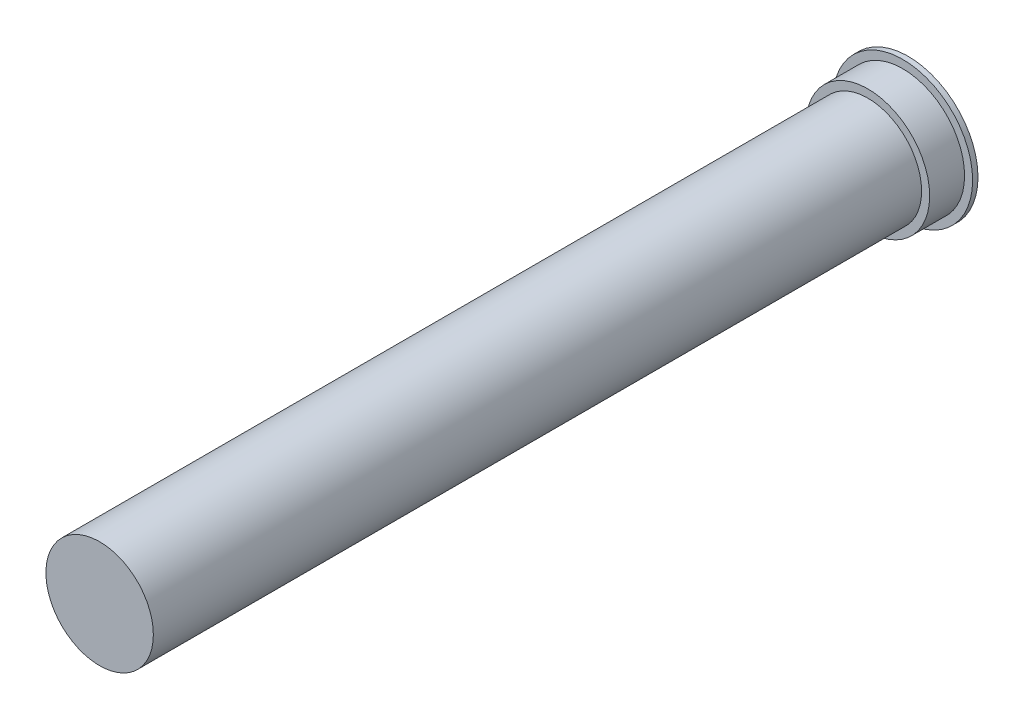
SolidWorks part; units mm, degrees
ref_plane "Front Plane" through (0, 0, 0) normal (0, 0, 1) x (1, 0, 0)
ref_plane "Top Plane" through (0, 0, 0) normal (0, 1, 0) x (1, 0, 0)
ref_plane "Right Plane" through (0, 0, 0) normal (1, 0, 0) x (0, 0, -1)
sketch "Sketch2" plane through (0, 0, 0) normal (0, 0, 1) x (1, 0, 0)
  circle A0 centre (0, 0) radius 20
  circle A1 centre (0, 0) radius 19
  circle A2 centre (0, 0) radius 25
  circle A3 centre (0, 0) radius 23
  circle A4 centre (0, 0) radius 26
  dimension "D1" = 40
  dimension "D3" = 50
  dimension "D2" = 1
  dimension "D4" = 2
  dimension "D5" = 1
extrude "Boss-Extrude1" add sketch "Sketch2" along normal blind 300 contours A0 A1 region at (-19.4343, 0, 0)
sketch "Sketch3" plane through (0, 0, 300) normal (0, 0, 1) x (1, 0, 0)
  circle A1 centre (0, 0) radius 20
  circle A2 centre (0, 0) radius 20
  dimension "D1" = 0
extrude "Boss-Extrude2" add sketch "Sketch3" along normal blind 1
extrude "Boss-Extrude3" add sketch "Sketch2<4>" along normal blind 15 contours A3 A0 region at (-22.3495, 0, 0)
sketch "Sketch2<4>" plane through (0, 0, 0) normal (0, 0, 1) x (1, 0, 0) same geometry as "Sketch2"
extrude "Boss-Extrude4" add sketch "Sketch2<5>" along normal blind 2 contours A2 A3 | A4 A2 region at (-24.2929, 0, 0) region at (-25.2646, 0, 0)
sketch "Sketch2<5>" plane through (0, 0, 0) normal (0, 0, 1) x (1, 0, 0) same geometry as "Sketch2"
